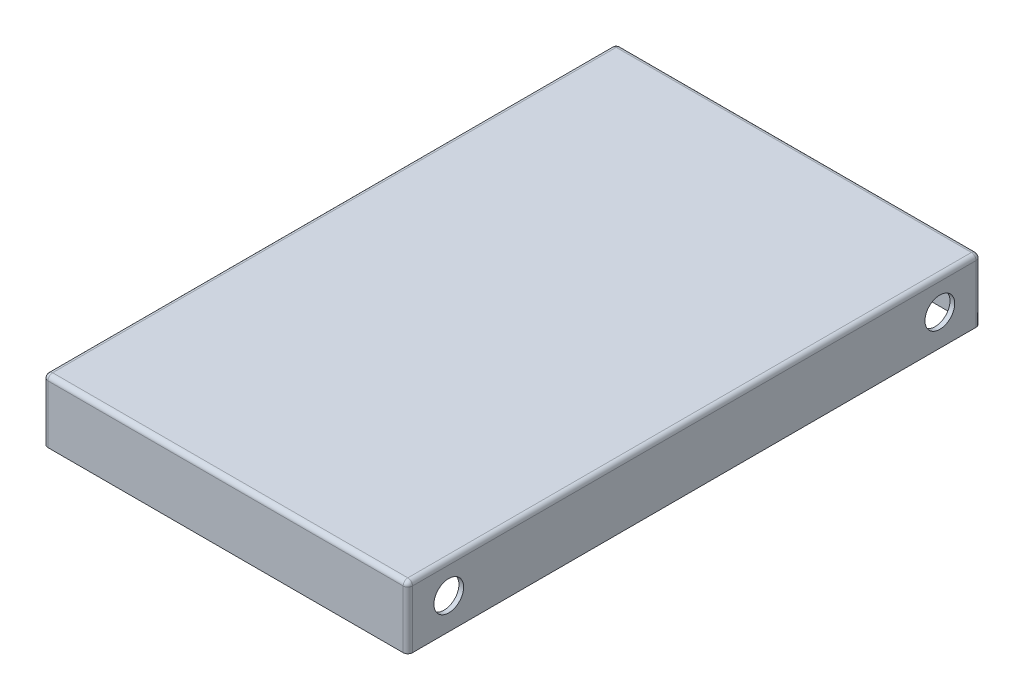
SolidWorks part; units mm, degrees
ref_plane "Front Plane" through (0, 0, 0) normal (0, 0, 1) x (1, 0, 0)
ref_plane "Top Plane" through (0, 0, 0) normal (0, 1, 0) x (1, 0, 0)
ref_plane "Right Plane" through (0, 0, 0) normal (1, 0, 0) x (0, 0, -1)
sketch "Sketch1" plane through (0, 0, 0) normal (0, 1, 0) x (1, 0, 0)
  line L1 (155.575, -244.475) -> (-155.575, -244.475)
  line L2 (155.575, -244.475) -> (155.575, 244.475)
  line L3 (155.575, 244.475) -> (-155.575, 244.475)
  line L4 (-155.575, -244.475) -> (-155.575, 244.475)
  line L5 (155.575, -244.475) -> (-155.575, 244.475) construction
  line L6 (155.575, 244.475) -> (-155.575, -244.475) construction
  point P0 (0, 0)
  dimension "D1" = 488.95
  dimension "D2" = 311.15
extrude "Boss-Extrude1" add sketch "Sketch1" along normal blind 53.34
fillet "Fillet1" radius 4 8 edges at (0, 53.34, -244.475) (155.575, 53.34, 0) (0, 53.34, 244.475) (-155.575, 53.34, 0) (-155.575, 26.67, -244.475) (155.575, 26.67, -244.475) (-155.575, 26.67, 244.475) (155.575, 26.67, 244.475)
shell "Shell1" thickness 4 removed face at (0, 0, 0)
sketch "Sketch2" plane through (155.575, 0, 0) normal (1, 0, 0) x (0, 0, -1)
  line L0 (0, 0) -> (0, 26.67) construction
  line L1 (-240.475, 0) -> (240.475, 0) construction
  line L2 (0, 26.67) -> (209.55, 26.67) construction
  line L3 (0, 26.67) -> (-209.55, 26.67) construction
  line L4 (0, 26.67) -> (0, 53.34) construction
  line L5 (-240.475, 53.34) -> (240.475, 53.34) construction
  circle A0 centre (-209.55, 26.67) radius 12.6794
  circle A1 centre (209.55, 26.67) radius 12.6794
  dimension "D1" = 419.1
extrude "Cut-Extrude1" cut sketch "Sketch2" against normal through all
